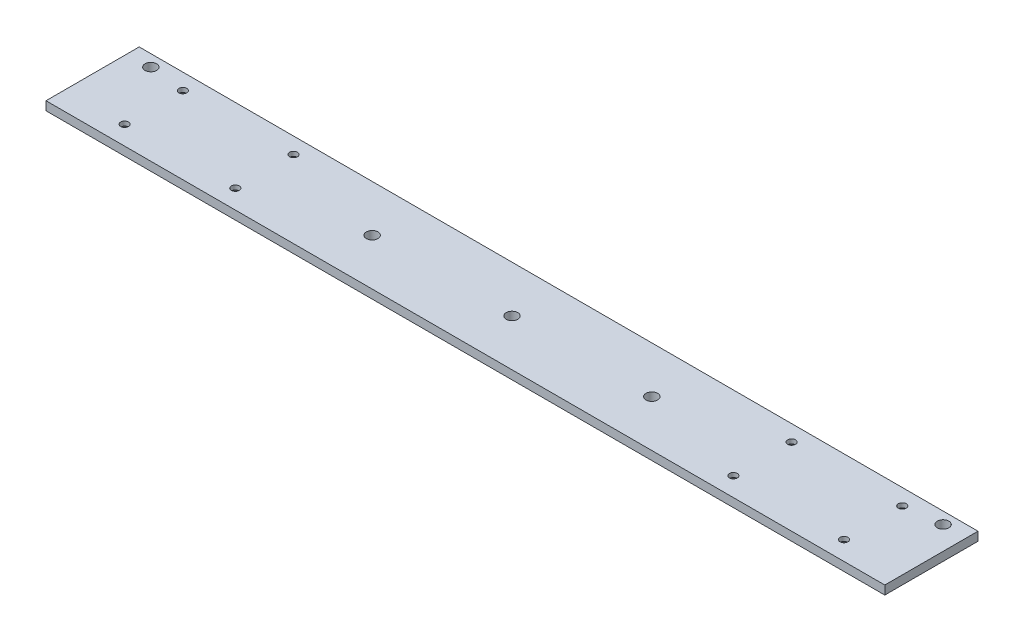
SolidWorks part; units mm, degrees
material "6061 Alloy"
ref_plane "Front Plane" through (0, 0, 0) normal (0, 0, 1) x (1, 0, 0)
ref_plane "Top Plane" through (0, 0, 0) normal (0, 1, 0) x (1, 0, 0)
ref_plane "Right Plane" through (0, 0, 0) normal (1, 0, 0) x (0, 0, -1)
sketch "Sketch1" plane through (0, 0, 0) normal (0, 1, 0) x (1, 0, 0)
  line L1 (0, 0) -> (457.2, 0)
  line L2 (0, 0) -> (0, 50.8)
  line L3 (0, 50.8) -> (457.2, 50.8)
  line L4 (457.2, 0) -> (457.2, 50.8)
  dimension "D1" = 457.2
  dimension "D2" = 50.8
extrude "Boss-Extrude1" add sketch "Sketch1" along normal blind 4.7625
sketch "Sketch2" plane through (0, 4.7625, 0) normal (0, 1, 0) x (1, 0, 0)
  line L0 (0, 0) -> (457.2, 0) construction
  line L1 (0, 50.8) -> (0, 0) construction
  circle A0 centre (12.7, 44.45) radius 3.175
  circle A1 centre (444.5, 44.45) radius 3.175
  dimension "D1" = 44.45
  dimension "D2" = 44.45
  dimension "D3" = 12.7
  dimension "D4" = 444.5
extrude "Cut-Extrude1" cut sketch "Sketch2" against normal blind 244.602
sketch "Sketch3" plane through (0, 4.7625, 0) normal (0, 1, 0) x (1, 0, 0)
  line L0 (457.2, 50.8) -> (0, 50.8) construction
  line L1 (457.2, 0) -> (457.2, 50.8) construction
  circle A0 centre (152.4, 25.4) radius 3.175
  circle A1 centre (304.8, 25.4) radius 3.175
  circle A2 centre (228.6, 25.4) radius 3.175
  dimension "D1" = 25.4
  dimension "D2" = 25.4
  dimension "D3" = 25.4
  dimension "D4" = 76.2
  dimension "D5" = 228.6
  dimension "D6" = 76.2
extrude "Cut-Extrude2" cut sketch "Sketch3" against normal blind 244.602
sketch "Sketch4" plane through (0, 4.7625, 0) normal (0, 1, 0) x (1, 0, 0)
  line L0 (457.2, 50.8) -> (0, 50.8) construction
  line L1 (0, 50.8) -> (0, 0) construction
  line L2 (457.2, 0) -> (457.2, 50.8) construction
  circle A0 centre (114.3, 25.4) radius 3.175
  circle A1 centre (342.9, 25.4) radius 3.175
  dimension "D1" = 25.4
  dimension "D4" = 114.3
  dimension "D2" = 25.4
  dimension "D3" = 114.3
hole_wizard "CSK for #8 Flat Head Machine Screw1" positions "Sketch8" profile "Sketch7" countersink size "#8" standard "ANSI Inch" end condition through all
sketch "Sketch8" plane through (0, 0, 0) normal (0, -1, 0) x (-1, 0, 0)
  point P0 (-424.6625, 42.0688)
  point P3 (-424.6625, 10.3188)
  point P6 (-364.3375, 10.3188)
  point P9 (-364.3375, 42.0688)
  point P12 (-92.8625, 42.0688)
  point P15 (-92.8625, 10.3188)
  point P18 (-32.5375, 10.3188)
  point P21 (-32.5375, 42.0688)
sketch "Sketch7" plane through (424.6625, 0, -42.0688) normal (1, 0, 0) x (0, 0, -1)
  line L0 (0, 0) -> (0, 4.7625)
  line L1 (0, 4.7625) -> (2.1526, 4.7625)
  line L2 (2.1526, 4.7625) -> (2.1526, 2.3741)
  line L3 (2.1526, 2.3741) -> (4.2164, 0)
  line L5 (4.2164, 0) -> (0, 0)
  line L6 (-2.1527, 2.3741) -> (-4.2164, 0) construction
  line L11 (0, -6.35) -> (0, 107.95) construction
  dimension "Thru Hole Dia." = 4.3053
  dimension "Thru Hole Depth" = 4.7625
  dimension "Near C'Sink Dia." = 8.4328
  dimension "Near C'Sink Angle" = 82
